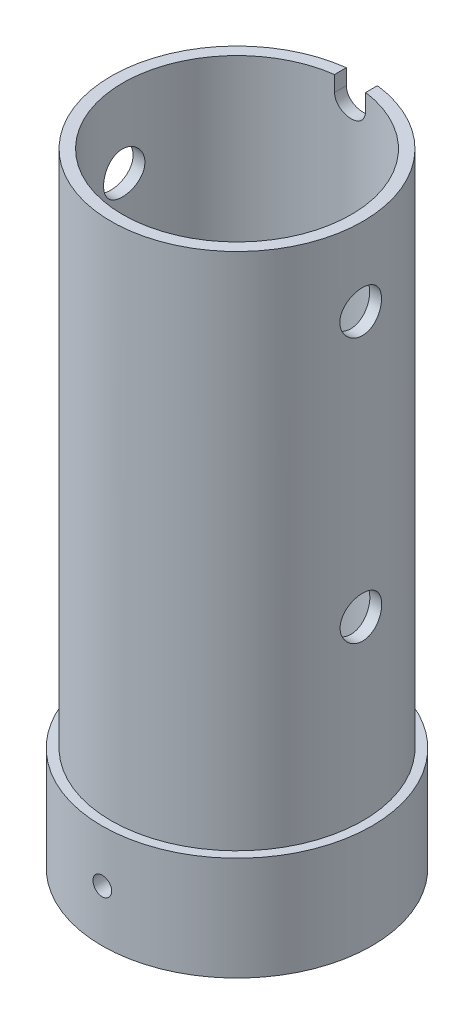
SolidWorks part; units mm, degrees
ref_plane "前视基准面" through (0, 0, 0) normal (0, 0, 1) x (1, 0, 0)
ref_plane "上视基准面" through (0, 0, 0) normal (0, 1, 0) x (1, 0, 0)
ref_plane "右视基准面" through (0, 0, 0) normal (1, 0, 0) x (0, 0, -1)
sketch "草图1" plane through (0, 0, 0) normal (0, 1, 0) x (1, 0, 0)
  circle A0 centre (0, 0) radius 26
  circle A1 centre (0, 0) radius 22
  dimension "D1" = 52
  dimension "D2" = 44
extrude "凸台-拉伸1" add sketch "草图1" along normal blind 20
sketch "草图3" plane through (0, 20, 0) normal (0, 1, 0) x (1, 0, 0)
  circle A0 centre (0, 0) radius 22
  circle A1 centre (0, 0) radius 24.25
  dimension "D1" = 48.5
extrude "凸台-拉伸2" add sketch "草图3" along normal blind 100
sketch "草图4" plane through (0, 0, 0) normal (0, 0, 1) x (1, 0, 0)
  line L0 (-26, 0) -> (26, 0) construction
  line L1 (24.25, 120) -> (-24.25, 120) construction
  line L2 (-3, 120) -> (3, 120)
  line L3 (-3, 120) -> (-3, 117)
  line L5 (3, 120) -> (3, 117)
  line L6 (0, 0) -> (0, 120) construction
  circle A0 centre (0, 10) radius 1.8
  arc A1 (-3, 117) -> (3, 117) centre (0, 117) ccw
  point P11 (0, 0)
  dimension "D1" = 10
  dimension "D2" = 3.6
  dimension "D3" = 3
  dimension "D4" = 3
extrude "切除-拉伸1" cut sketch "草图4" against normal blind 100
sketch "草图5" plane through (0, 0, 0) normal (0, 0, 1) x (1, 0, 0)
  circle A0 centre (0, 10) radius 1.8
extrude "切除-拉伸2" cut sketch "草图5" along normal blind 100
sketch "草图6" plane through (0, 0, 0) normal (1, 0, 0) x (0, 0, -1)
  line L0 (0, 0) -> (-0.1028, 120) construction
  line L1 (21.7945, 120) -> (-22, 120) construction
  circle A0 centre (-0.0899, 105) radius 4
  circle A1 centre (-0.0462, 54) radius 4
  dimension "D1" = 51
  dimension "D2" = 15
  dimension "D3" = 8
  dimension "D4" = 8
extrude "切除-拉伸3" cut sketch "草图6" against normal blind 100 and the other way blind 100
